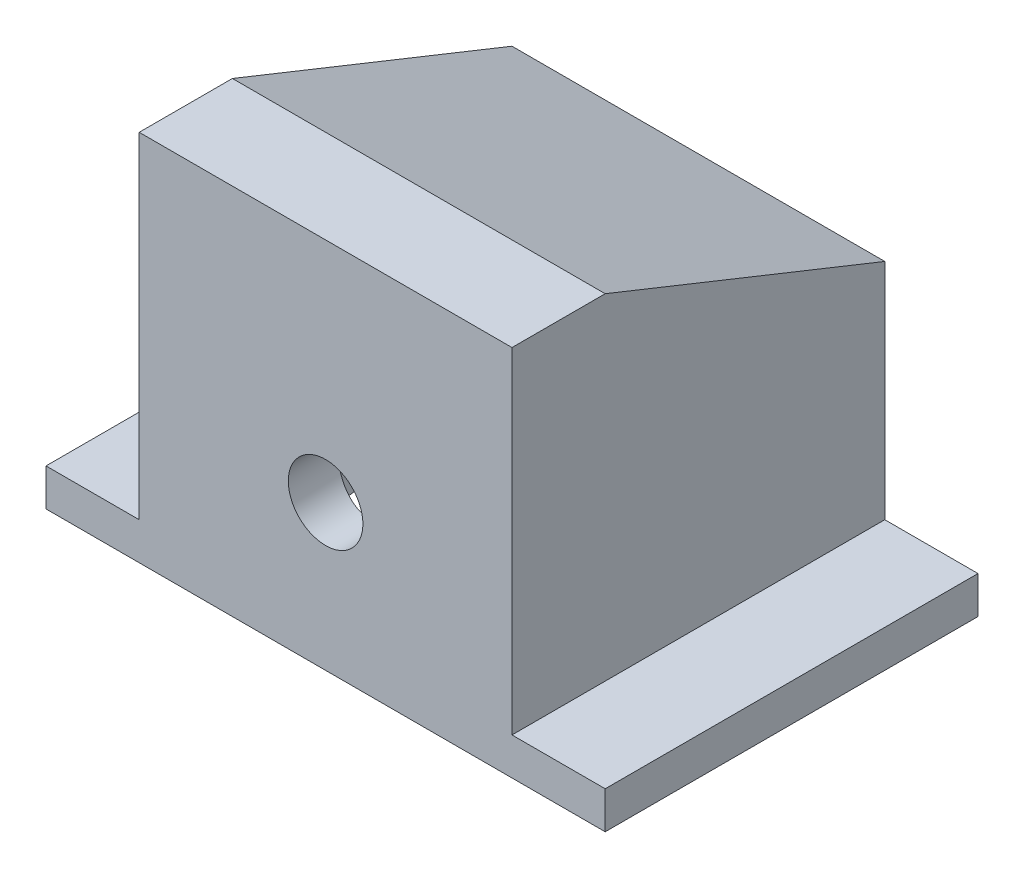
SolidWorks part; units mm, degrees
ref_plane "Ebene vorne" through (0, 0, 0) normal (0, 0, 1) x (1, 0, 0)
ref_plane "Ebene oben" through (0, 0, 0) normal (0, 1, 0) x (1, 0, 0)
ref_plane "Ebene rechts" through (0, 0, 0) normal (1, 0, 0) x (0, 0, -1)
sketch "Sketch1" plane through (0, 0, 0) normal (0, 1, 0) x (1, 0, 0)
  line L1 (0, 0) -> (20, 0)
  line L2 (0, 0) -> (0, 20)
  line L3 (0, 20) -> (20, 20)
  line L4 (20, 0) -> (20, 20)
  dimension "D1" = 20
  dimension "D2" = 20
extrude "Boss-Extrude1" add sketch "Sketch1" along normal blind 20
fillet "Chamfer1" radius 6 1 edges at (10, 20, -20) profile chamfer first distance on face at (10, 10, -20)
sketch "Sketch2" plane through (0, 0, 0) normal (0, -1, 0) x (1, 0, 0)
  line L0 (20, -10) -> (0, -10) construction
  line L1 (20, 0) -> (20, -20) construction
  line L2 (0, -20) -> (0, 0) construction
  circle A0 centre (10, -10) radius 7.6
  dimension "D1" = 15.2
extrude "Cut-Extrude1" cut sketch "Sketch2" against normal blind 13
sketch "Sketch3" plane through (0, 0, -20) normal (0, 0, -1) x (-1, 0, 0)
  line L0 (-10, 0) -> (-10, 14) construction
  line L1 (-20, 0) -> (0, 0) construction
  line L2 (0, 14) -> (-20, 14) construction
  line L3 (-17.6, 13) -> (-2.4, 13) construction
  line L4 (-17.6, 13) -> (-2.4, 13) construction
  circle A0 centre (-10, 7.8) radius 2
  dimension "D1" = 4
  dimension "D2" = 5.2
extrude "Cut-Extrude2" cut sketch "Sketch3" against normal up to surface (20 mm away) up to face at (10, 10, 0)
sketch "Sketch4" plane through (0, 0, 0) normal (0, -1, 0) x (-1, 0, 0)
  line L0 (-10, 20) -> (-10, 0) construction
  line L11 (-20, 0) -> (-25, 0)
  line L12 (-20, 0) -> (-20, 20)
  line L13 (-20, 20) -> (-25, 20)
  line L14 (-25, 0) -> (-25, 20)
  line L15 (-20, 20) -> (0, 20) construction
  line L16 (0, 0) -> (-20, 0) construction
  line L17 (5, 0) -> (5, 20)
  line L18 (0, 20) -> (5, 20)
  line L19 (0, 0) -> (0, 20)
  line L20 (0, 0) -> (5, 0)
  dimension "D1" = 30
extrude "Boss-Extrude2" add sketch "Sketch4" against normal blind 2
